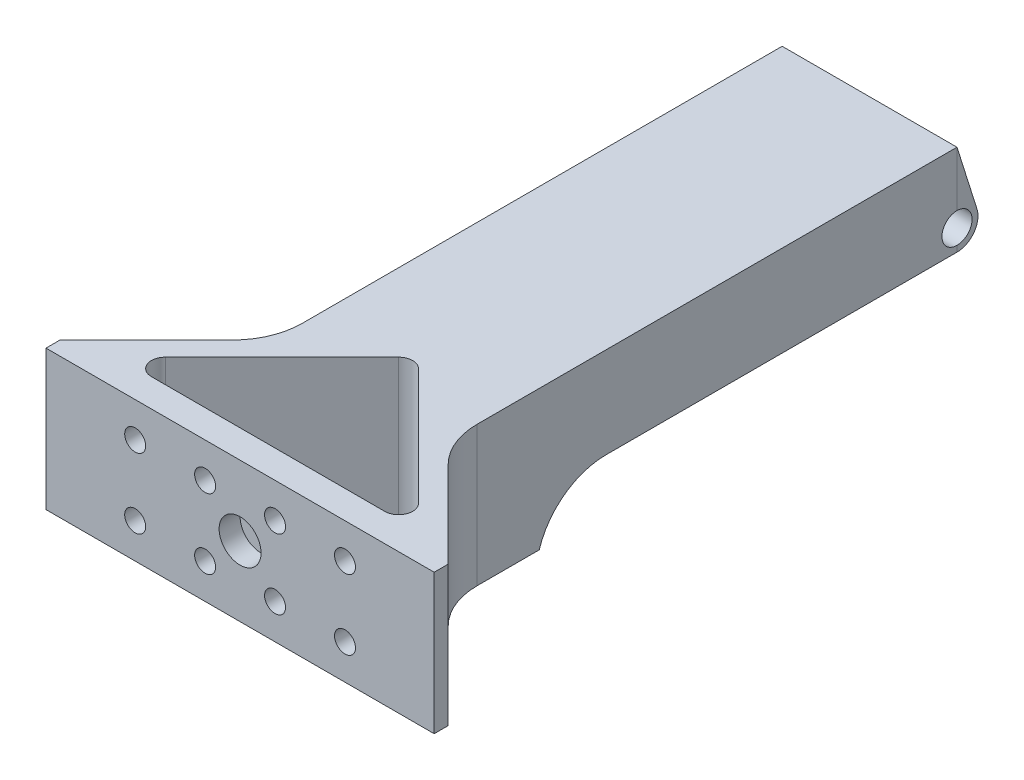
SolidWorks part; units mm, degrees
material "6061 합금"
ref_plane "정면" through (0, 0, 0) normal (0, 0, 1) x (1, 0, 0)
ref_plane "윗면" through (0, 0, 0) normal (0, 1, 0) x (1, 0, 0)
ref_plane "우측면" through (0, 0, 0) normal (1, 0, 0) x (0, 0, -1)
sketch "스케치1" plane through (0, 0, 0) normal (0, 1, 0) x (1, 0, 0)
  line L0 (27.75, 94.3974) -> (27.75, -27.5062) construction
  line L1 (40.2477, 90) -> (15.2523, 90)
  line L2 (0, 2) -> (0, 0)
  line L3 (15.2523, 17.2523) -> (0, 2)
  line L4 (40.2477, 90) -> (40.2477, 17.2523)
  line L5 (40.2477, 17.2523) -> (55.5, 2)
  line L6 (55.5, 2) -> (55.5, 0)
  line L7 (55.5, 0) -> (0, 0)
  line L8 (15.2523, 90) -> (15.2523, 17.2523)
  line L9 (11.0711, 4) -> (44.4289, 4)
  line L11 (45.8431, 7.4142) -> (29.1642, 24.0931)
  line L14 (9.6569, 7.4142) -> (26.3358, 24.0931)
  arc A0 (9.6569, 7.4142) -> (11.0711, 4) centre (11.0711, 6) ccw
  arc A1 (29.1642, 24.0931) -> (26.3358, 24.0931) centre (27.75, 22.6789) ccw
  arc A2 (44.4289, 4) -> (45.8431, 7.4142) centre (44.4289, 6) ccw
  point P12 (27.75, 90)
  point P18 (27.75, 5)
  point P20 (27.75, 25.4481)
  dimension "D12" = 3
  dimension "D9" = 3
  dimension "D8" = 4
  dimension "D10" = 4
  dimension "D11" = 4
  dimension "D1" = 55.5
  dimension "D2" = 135
  dimension "D3" = 2
  dimension "D4" = 21.57
  dimension "D5" = 90
  dimension "D6" = 12.4977
  dimension "D7" = 4
extrude "보스-돌출1" add sketch "스케치1" along normal blind 20
sketch "스케치2" plane through (0, 0, 0) normal (0, 0, 1) x (1, 0, 0)
  line L0 (0, 20) -> (0, 0) construction
  line L1 (0, 20) -> (55.5, 20) construction
  line L2 (0, 10) -> (60.2338, 10) construction
  line L3 (27.75, 23.0111) -> (27.75, -4.7654) construction
  circle A0 centre (12.75, 15) radius 1.5
  circle A1 centre (22.75, 15) radius 1.5
  circle A2 centre (32.75, 15) radius 1.5
  circle A3 centre (42.75, 15) radius 1.5
  circle A4 centre (42.75, 5) radius 1.5
  circle A5 centre (32.75, 5) radius 1.5
  circle A6 centre (22.75, 5) radius 1.5
  circle A7 centre (12.75, 5) radius 1.5
  dimension "D1" = 12.75
  dimension "D3" = 10
  dimension "D4" = 3
  dimension "D5" = 3
  dimension "D2" = 5
extrude "컷-돌출1" cut sketch "스케치2" against normal blind 5
sketch "스케치3" plane through (0, 0, 0) normal (0, 0, 1) x (1, 0, 0)
  line L3 (55, 0) -> (-55, 0) construction
  line L4 (55.5, 20) -> (55.5, 0) construction
  circle A0 centre (27.75, 10) radius 3
  dimension "D1" = 6
  dimension "D2" = 10
  dimension "D3" = 27.75
extrude "컷-돌출2" cut sketch "스케치3" against normal blind 3
ref_plane "평면1" through (15.25, 0, 0) normal (1, 0, 0) x (0, 0, -1)
sketch "스케치4" plane through (0, 0, 0) normal (0, -1, 0) x (1, 0, 0)
  line L0 (15.25, -11) -> (15.25, 11) construction
  line L1 (40.2477, -90) -> (15.25, -90)
  line L2 (40.2477, -90) -> (40.2477, -30.27)
  line L3 (40.2477, -30.27) -> (15.25, -30.27)
  line L4 (15.25, -90) -> (15.25, -30.27)
  dimension "D1" = 59.73
extrude "컷-돌출3" cut sketch "스케치4" against normal blind 7
sketch "스케치5" plane through (15.2523, 0, 0) normal (-1, 0, 0) x (0, 0, 1)
  line L0 (-90, 20) -> (-92.8924, 10.8041)
  line L1 (-90, 20) -> (-90, 7)
  line L2 (-30.27, 7) -> (-90, 7) construction
  arc A0 (-92.8924, 10.8041) -> (-90, 7) centre (-90.0022, 10) ccw
  circle A1 centre (-90.0022, 10) radius 1.5
  line M8 (-90, 20) -> (-90, 7)
  dimension "D3" = 3
  dimension "D4" = 3
  dimension "D1" = 17.46
  dimension "D2" = 9.64
extrude "보스-돌출2" add sketch "스케치5" against normal blind 25 contours L1 A1 | A1 L0 A0 M8 region at (15.2523, 12.2584, -91.2029) region at (15.2523, 10, -90.6376)
sketch "스케치6" plane through (15.2523, 0, 0) normal (-1, 0, 0) x (0, 0, 1)
  circle A0 centre (-90.0022, 10) radius 2.15
  dimension "D1" = 4.3
extrude "컷-돌출4" cut sketch "스케치6" against normal through all
ref_plane "평면2" through (28, 0, 0) normal (1, 0, 0) x (0, 0, -1)
ref_plane "평면6" through (9.4585, -19.1033, -9.4585) normal (0.4056, -0.8192, -0.4056) x (-0.7071, 0, -0.7071)
ref_plane "평면7" through (27.7477, 0, 0) normal (1, 0, 0) x (0, 0, -1)
sketch "스케치13" plane through (15.2523, 0, 0) normal (-1, 0, 0) x (0, 0, 1)
  circle A0 centre (-90.0022, 10) radius 2
  dimension "D1" = 4
sketch "스케치14" plane through (40.2477, 0, 0) normal (1, 0, 0) x (0, 0, -1)
  circle A0 centre (90.0022, 10) radius 2
fillet "필렛4" radius 10 2 edges at (15.2523, 10, -17.2523) (40.2477, 10, -17.2523)
fillet "필렛5" radius 10 1 edges at (27.75, 7, -30.27)
